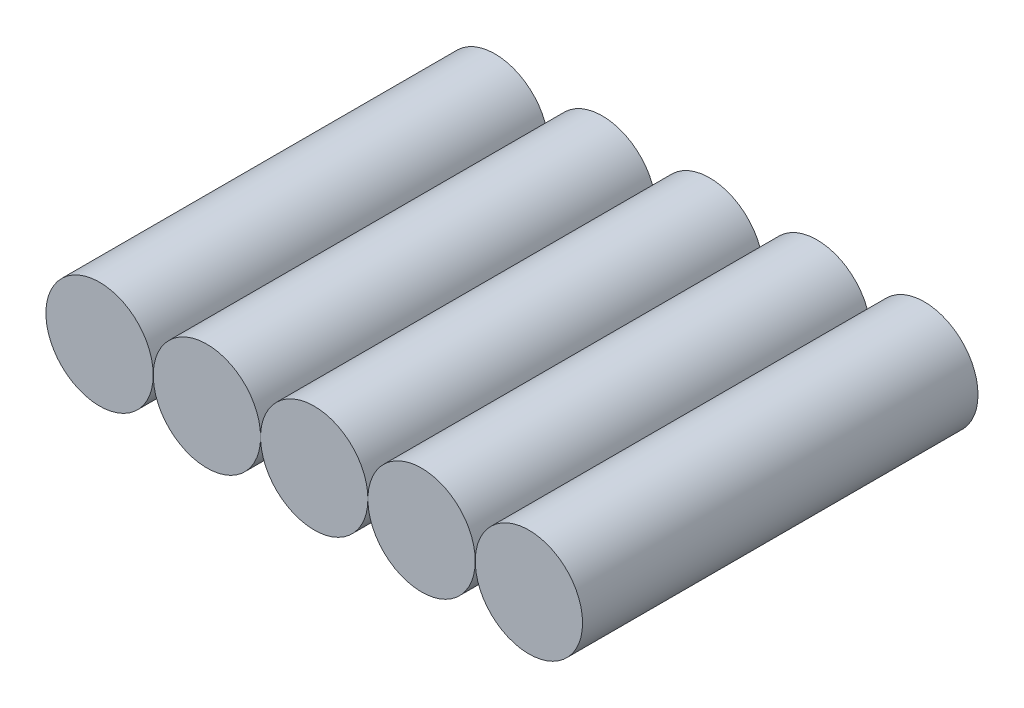
SolidWorks part; units mm, degrees
ref_plane "Front Plane" through (0, 0, 0) normal (0, 0, 1) x (1, 0, 0)
ref_plane "Top Plane" through (0, 0, 0) normal (0, 1, 0) x (1, 0, 0)
ref_plane "Right Plane" through (0, 0, 0) normal (1, 0, 0) x (0, 0, -1)
sketch "Sketch1" plane through (0, 0, 0) normal (0, 0, 1) x (1, 0, 0)
  line L0 (0, 0) -> (28.1527, 0) construction
  circle A0 centre (0, 0) radius 9.5
  circle A1 centre (19, 0) radius 9.5
  circle A2 centre (-19, 0) radius 9.5
  circle A3 centre (-38, 0) radius 9.5
  circle A4 centre (38, 0) radius 9.5
  dimension "D1" = 19
extrude "Boss-Extrude1" add sketch "Sketch1" along normal blind 35 and the other way blind 35 contours A2 L0 | A0 L0 | A1 L0 | L0 A1 | L0 A0 | L0 A2 | L0 A3 | A3 L0 | A4 L0 | L0 A4 region at (0, -9.2313, 0) region at (-38, 0, 0) region at (-19, 0, 0) region at (38, 0, 0) region at (19, 9.2313, 0)
